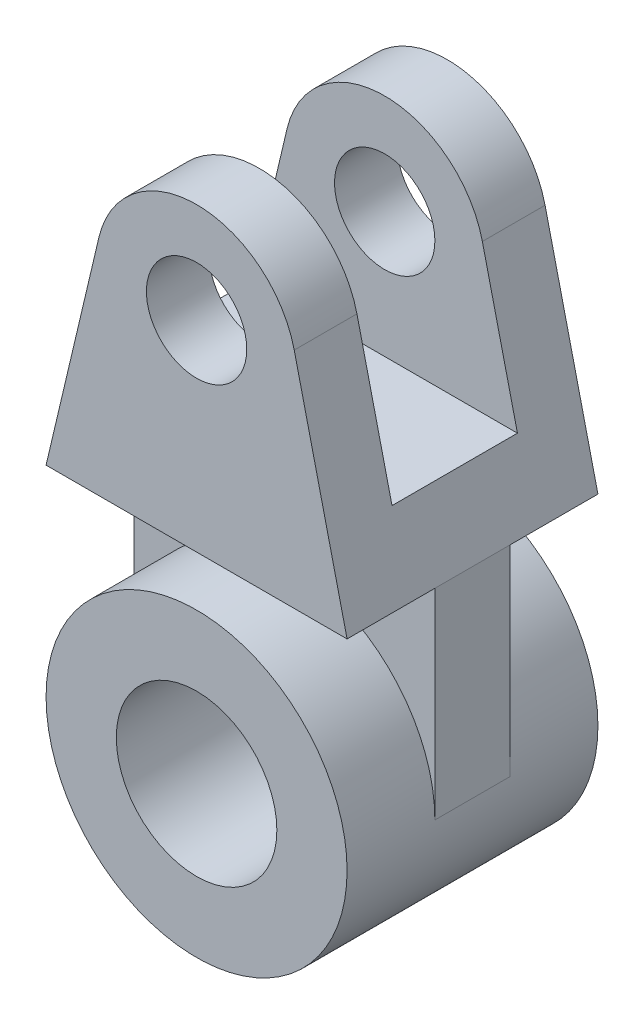
SolidWorks part; units mm, degrees
material "Titanium Ti-8Mn, Annealed"
ref_plane "Front Plane" through (0, 0, 0) normal (0, 0, 1) x (1, 0, 0)
ref_plane "Top Plane" through (0, 0, 0) normal (0, 1, 0) x (1, 0, 0)
ref_plane "Right Plane" through (0, 0, 0) normal (1, 0, 0) x (0, 0, -1)
sketch "Sketch1" plane through (0, 0, 0) normal (0, 0, 1) x (1, 0, 0)
  circle A0 centre (0, 0) radius 30
  circle A1 centre (0, 0) radius 16
  dimension "D1" = 60
  dimension "D2" = 32
extrude "Boss-Extrude1" add sketch "Sketch1" against normal mid plane 50
sketch "Sketch2" plane through (0, 0, 0) normal (0, 0, 1) x (1, 0, 0)
  line L0 (0, 0) -> (0, 40) construction
  line L1 (30, 0) -> (30, 40)
  line L2 (-30, 0) -> (-30, 40)
  line L3 (-30, 40) -> (30, 40)
  circle A0 centre (0, 0) radius 30 construction
  circle A1 centre (0, 0) radius 30
  dimension "D1" = 40
  dimension "D2" = 30
  dimension "D3" = 30
extrude "Boss-Extrude5" add sketch "Sketch2" along normal mid plane 15 contours A1 L0 L3 L2 | L0 A1 L1 L3 region at (-18.2503, 30.4172, 0) region at (18.2503, 30.4172, 0)
sketch "Sketch6" plane through (0, 40, 0) normal (0, 1, 0) x (1, 0, 0)
  line L1 (-30, -25) -> (30, -25) construction
  line L2 (-30, -25) -> (-30, 25) construction
  line L3 (-30, 25) -> (30, 25) construction
  line L4 (30, -25) -> (30, 25) construction
  line L5 (-30, -25) -> (30, 25) construction
  line L6 (-30, 25) -> (30, -25) construction
  point P0 (0, 0)
sketch "Sketch7" plane through (0, 0, 25) normal (0, 0, 1) x (1, 0, 0)
  line L0 (0, 0) -> (0, 80) construction
  line L1 (-30, 40) -> (30, 40) construction
  line L2 (-30, 40) -> (30, 40)
  line L3 (-19.4642, 84.5982) -> (-30, 40)
  line L4 (30, 40) -> (19.4642, 84.5982)
  line L5 (-26.4564, 55) -> (26.4564, 55)
  arc A0 (19.4642, 84.5982) -> (-19.4642, 84.5982) centre (0, 80) ccw
  circle A1 centre (0, 80) radius 10
  dimension "D2" = 15
  dimension "D1" = 80
extrude "Boss-Extrude6" add sketch "Sketch7" against normal blind 50 contours L2 L0 L5 L3 | L0 L2 L4 L5 region at (-14.1326, 47.3431, 25) region at (14.1326, 47.3431, 25)
extrude "Boss-Extrude7" add sketch "Sketch7<3>" against normal blind 12.5 contours L4 A0 L3 L5 A1 region at (-22.2843, 69.6394, 25)
sketch "Sketch7<3>" plane through (0, 0, 25) normal (0, 0, 1) x (1, 0, 0) same geometry as "Sketch7"
mirror "Mirror2" about plane through (0, 0, 0) normal (0, 0, 1) of "Boss-Extrude7"
